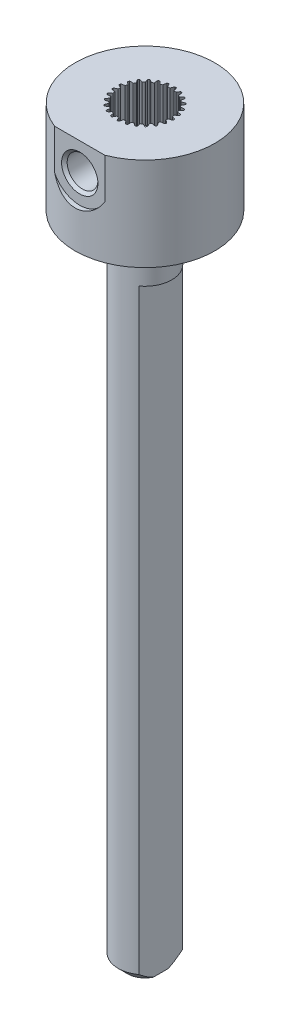
SolidWorks part; units mm, degrees
material "PBT General Purpose"
ref_plane "Front Plane" through (0, 0, 0) normal (0, 0, 1) x (1, 0, 0)
ref_plane "Top Plane" through (0, 0, 0) normal (0, 1, 0) x (1, 0, 0)
ref_plane "Right Plane" through (0, 0, 0) normal (1, 0, 0) x (0, 0, -1)
sketch "Sketch1" plane through (0, 0, 0) normal (0, 1, 0) x (1, 0, 0)
  circle A0 centre (0, 0) radius 2.875
  dimension "D1" = 5.75
extrude "Boss-Extrude1" add sketch "Sketch1" along normal mid plane 70
chamfer "Chamfer1" distance 1 angle 45 1 edges at (0, -35, 2.875)
sketch "Sketch2" plane through (0, 35, 0) normal (0, 1, 0) x (1, 0, 0)
  circle A0 centre (0, 0) radius 7.5
  dimension "D1" = 15
extrude "Boss-Extrude2" add sketch "Sketch2" along normal blind 10
sketch "Sketch3" plane through (0, 45, 0) normal (0, 1, 0) x (1, 0, 0)
  circle A0 centre (0, 0) radius 2.5
  dimension "D1" = 5
extrude "Cut-Extrude1" cut sketch "Sketch3" against normal blind 6
ref_plane "Plane1" through (0, 0, 10) normal (0, 0, 1) x (1, 0, 0)
sketch "Sketch5" plane through (0, 0, 10) normal (0, 0, 1) x (1, 0, 0)
  line L0 (0, 42) -> (0, 45) construction
  line L1 (2.5, 45) -> (-2.5, 45) construction
  line L2 (-3, 42) -> (-3, 45)
  line L3 (7.5, 45) -> (-7.5, 45) construction
  line L4 (-3, 45) -> (3, 45)
  line L5 (3, 45) -> (3, 42)
  arc A0 (-3, 42) -> (3, 42) centre (0, 42) ccw
  dimension "D1" = 6
  dimension "D2" = 3
extrude "Cut-Extrude3" cut sketch "Sketch5" against normal blind 3
sketch "Sketch4" plane through (0, 0, 10) normal (0, 0, 1) x (1, 0, 0)
  line L0 (0, 42) -> (0, 45) construction
  line L1 (7.5, 45) -> (-7.5, 45) construction
  circle A0 centre (0, 42) radius 1.65
  arc A2 (-2.6926, 40.6771) -> (2.6926, 40.6771) centre (0, 42) ccw construction
  dimension "D1" = 3.3
extrude "Cut-Extrude2" cut sketch "Sketch4" against normal up to next
chamfer "Chamfer2" distance 0.3 angle 45 1 edges at (1.65, 42, 7)
sketch "Sketch7" plane through (0, 45, 0) normal (0, 1, 0) x (1, 0, 0)
  line L1201 (2.7391, 0.4913) -> (2.7926, 0.5169)
  line L1202 (2.7002, 0.4763) -> (2.7391, 0.4913)
  line L1203 (2.7144, 0.3878) -> (2.7002, 0.4763)
  line L1204 (2.7256, 0.2988) -> (2.7144, 0.3878)
  line L1205 (2.7339, 0.2095) -> (2.7256, 0.2988)
  line L1206 (2.7753, 0.2046) -> (2.7339, 0.2095)
  line L1207 (2.8336, 0.193) -> (2.7753, 0.2046)
  line L1208 (2.8706, 0.1829) -> (2.8336, 0.193)
  line L1209 (2.8995, 0.1744) -> (2.8706, 0.1829)
  line L1210 (2.9507, 0.1568) -> (2.8995, 0.1744)
  line L1211 (2.9703, 0.1492) -> (2.9507, 0.1568)
  line L1212 (3.0285, 0.125) -> (2.9703, 0.1492)
  line L1213 (3.0613, 0.1091) -> (3.0285, 0.125)
  line L1214 (3.115, 0.0827) -> (3.0613, 0.1091)
  line L1215 (3.116, 0.0273) -> (3.115, 0.0827)
  line L1216 (3.116, -0.028) -> (3.116, 0.0273)
  line L1217 (3.115, -0.0834) -> (3.116, -0.028)
  line L1218 (3.0613, -0.1098) -> (3.115, -0.0834)
  line L1219 (3.0285, -0.1256) -> (3.0613, -0.1098)
  line L1220 (2.9703, -0.1499) -> (3.0285, -0.1256)
  line L1221 (2.9507, -0.1575) -> (2.9703, -0.1499)
  line L1222 (2.8994, -0.1751) -> (2.9507, -0.1575)
  line L1223 (2.8705, -0.1837) -> (2.8994, -0.1751)
  line L1224 (2.8335, -0.1938) -> (2.8705, -0.1837)
  line L1225 (2.7753, -0.2053) -> (2.8335, -0.1938)
  line L1226 (2.7339, -0.2102) -> (2.7753, -0.2053)
  line L1227 (2.7256, -0.2995) -> (2.7339, -0.2102)
  line L1228 (2.7144, -0.3884) -> (2.7256, -0.2995)
  line L1229 (2.7002, -0.477) -> (2.7144, -0.3884)
  line L1230 (2.7391, -0.492) -> (2.7002, -0.477)
  line L1231 (2.7927, -0.5177) -> (2.7391, -0.492)
  line L1232 (2.8259, -0.5367) -> (2.7927, -0.5177)
  line L1233 (2.8518, -0.5521) -> (2.8259, -0.5367)
  line L1234 (2.8971, -0.5819) -> (2.8518, -0.5521)
  line L1235 (2.9141, -0.5942) -> (2.8971, -0.5819)
  line L1236 (2.9645, -0.6321) -> (2.9141, -0.5942)
  line L1237 (2.9924, -0.6557) -> (2.9645, -0.6321)
  line L1238 (3.0378, -0.6946) -> (2.9924, -0.6557)
  line L1239 (3.025, -0.7484) -> (3.0378, -0.6946)
  line L1240 (3.0112, -0.8021) -> (3.025, -0.7484)
  line L1241 (2.9965, -0.8554) -> (3.0112, -0.8021)
  line L1242 (2.938, -0.8676) -> (2.9965, -0.8554)
  line L1243 (2.9022, -0.8749) -> (2.938, -0.8676)
  line L1244 (2.8398, -0.8838) -> (2.9022, -0.8749)
  line L1245 (2.8189, -0.8864) -> (2.8398, -0.8838)
  line L1246 (2.7649, -0.8907) -> (2.8189, -0.8864)
  line L1247 (2.7347, -0.8917) -> (2.7649, -0.8907)
  line L1248 (2.6964, -0.8924) -> (2.7347, -0.8917)
  line L1249 (2.6372, -0.8891) -> (2.6964, -0.8924)
  line L1250 (2.5959, -0.8835) -> (2.6372, -0.8891)
  line L1251 (2.5656, -0.9679) -> (2.5959, -0.8835)
  line L1252 (2.5326, -1.0513) -> (2.5656, -0.9679)
  line L1253 (2.4969, -1.1335) -> (2.5326, -1.0513)
  line L1254 (2.5308, -1.1577) -> (2.4969, -1.1335)
  line L1255 (2.5763, -1.196) -> (2.5308, -1.1577)
  line L1256 (2.6038, -1.2226) -> (2.5763, -1.196)
  line L1257 (2.625, -1.244) -> (2.6038, -1.2226)
  line L1258 (2.6615, -1.2841) -> (2.625, -1.244)
  line L1259 (2.6749, -1.3003) -> (2.6615, -1.2841)
  line L1260 (2.7143, -1.3495) -> (2.6749, -1.3003)
  line L1261 (2.7354, -1.3793) -> (2.7143, -1.3495)
  line L1262 (2.7697, -1.4282) -> (2.7354, -1.3793)
  line L1263 (2.7439, -1.4772) -> (2.7697, -1.4282)
  line L1264 (2.7172, -1.5257) -> (2.7439, -1.4772)
  line L1265 (2.6897, -1.5737) -> (2.7172, -1.5257)
  line L1266 (2.63, -1.571) -> (2.6897, -1.5737)
  line L1267 (2.5935, -1.5691) -> (2.63, -1.571)
  line L1268 (2.5308, -1.5623) -> (2.5935, -1.5691)
  line L1269 (2.51, -1.5596) -> (2.5308, -1.5623)
  line L1270 (2.4566, -1.5503) -> (2.51, -1.5596)
  line L1271 (2.4271, -1.5438) -> (2.4566, -1.5503)
  line L1272 (2.3898, -1.5349) -> (2.4271, -1.5438)
  line L1273 (2.3333, -1.517) -> (2.3898, -1.5349)
  line L1274 (2.2947, -1.5013) -> (2.3333, -1.517)
  line L1275 (2.2444, -1.5755) -> (2.2947, -1.5013)
  line L1276 (2.1917, -1.6481) -> (2.2444, -1.5755)
  line L1277 (2.1366, -1.7189) -> (2.1917, -1.6481)
  line L1278 (2.1635, -1.7507) -> (2.1366, -1.7189)
  line L1279 (2.198, -1.7991) -> (2.1635, -1.7507)
  line L1280 (2.218, -1.8317) -> (2.198, -1.7991)
  line L1281 (2.2333, -1.8577) -> (2.218, -1.8317)
  line L1282 (2.2586, -1.9056) -> (2.2333, -1.8577)
  line L1283 (2.2676, -1.9246) -> (2.2586, -1.9056)
  line L1284 (2.2935, -1.9821) -> (2.2676, -1.9246)
  line L1285 (2.3065, -2.0162) -> (2.2935, -1.9821)
  line L1286 (2.3276, -2.0722) -> (2.3065, -2.0162)
  line L1287 (2.2904, -2.1132) -> (2.3276, -2.0722)
  line L1288 (2.2525, -2.1535) -> (2.2904, -2.1132)
  line L1289 (2.2139, -2.1932) -> (2.2525, -2.1535)
  line L1290 (2.1567, -2.1757) -> (2.2139, -2.1932)
  line L1291 (2.1219, -2.1648) -> (2.1567, -2.1757)
  line L1292 (2.0629, -2.1426) -> (2.1219, -2.1648)
  line L1293 (2.0434, -2.1348) -> (2.0629, -2.1426)
  line L1294 (1.9939, -2.1125) -> (2.0434, -2.1348)
  line L1295 (1.967, -2.0989) -> (1.9939, -2.1125)
  line L1296 (1.9331, -2.081) -> (1.967, -2.0989)
  line L1297 (1.8828, -2.0496) -> (1.9331, -2.081)
  line L1298 (1.8493, -2.0248) -> (1.8828, -2.0496)
  line L1299 (1.7821, -2.0842) -> (1.8493, -2.0248)
  line L1300 (1.713, -2.1413) -> (1.7821, -2.0842)
  line L1301 (1.6421, -2.1962) -> (1.713, -2.1413)
  line L1302 (1.6602, -2.2338) -> (1.6421, -2.1962)
  line L1303 (1.6816, -2.2892) -> (1.6602, -2.2338)
  line L1304 (1.6929, -2.3258) -> (1.6816, -2.2892)
  line L1305 (1.7012, -2.3548) -> (1.6929, -2.3258)
  line L1306 (1.7138, -2.4075) -> (1.7012, -2.3548)
  line L1307 (1.7178, -2.4281) -> (1.7138, -2.4075)
  line L1308 (1.7286, -2.4902) -> (1.7178, -2.4281)
  line L1309 (1.7327, -2.5265) -> (1.7286, -2.4902)
  line L1310 (1.7392, -2.5859) -> (1.7327, -2.5265)
  line L1311 (1.693, -2.6164) -> (1.7392, -2.5859)
  line L1312 (1.6463, -2.6461) -> (1.693, -2.6164)
  line L1313 (1.599, -2.6749) -> (1.6463, -2.6461)
  line L1314 (1.548, -2.6437) -> (1.599, -2.6749)
  line L1315 (1.517, -2.6245) -> (1.548, -2.6437)
  line L1316 (1.4653, -2.5883) -> (1.517, -2.6245)
  line L1317 (1.4484, -2.5759) -> (1.4653, -2.5883)
  line L1318 (1.406, -2.542) -> (1.4484, -2.5759)
  line L1319 (1.3833, -2.5221) -> (1.406, -2.542)
  line L1320 (1.355, -2.4964) -> (1.3833, -2.5221)
  line L1321 (1.314, -2.4534) -> (1.355, -2.4964)
  line L1322 (1.2878, -2.4211) -> (1.314, -2.4534)
  line L1323 (1.2079, -2.4619) -> (1.2878, -2.4211)
  line L1324 (1.1268, -2.5001) -> (1.2079, -2.4619)
  line L1325 (1.0444, -2.5356) -> (1.1268, -2.5001)
  line L1326 (1.0526, -2.5765) -> (1.0444, -2.5356)
  line L1327 (1.0596, -2.6355) -> (1.0526, -2.5765)
  line L1328 (1.0614, -2.6737) -> (1.0596, -2.6355)
  line L1329 (1.0622, -2.7038) -> (1.0614, -2.6737)
  line L1330 (1.0613, -2.758) -> (1.0622, -2.7038)
  line L1331 (1.0601, -2.779) -> (1.0613, -2.758)
  line L1332 (1.0551, -2.8419) -> (1.0601, -2.779)
  line L1333 (1.0501, -2.878) -> (1.0551, -2.8419)
  line L1334 (1.0416, -2.9372) -> (1.0501, -2.878)
  line L1335 (0.9892, -2.9552) -> (1.0416, -2.9372)
  line L1336 (0.9366, -2.9723) -> (0.9892, -2.9552)
  line L1337 (0.8837, -2.9885) -> (0.9366, -2.9723)
  line L1338 (0.842, -2.9456) -> (0.8837, -2.9885)
  line L1339 (0.8167, -2.9193) -> (0.842, -2.9456)
  line L1340 (0.7757, -2.8714) -> (0.8167, -2.9193)
  line L1341 (0.7623, -2.8552) -> (0.7757, -2.8714)
  line L1342 (0.7298, -2.8118) -> (0.7623, -2.8552)
  line L1343 (0.7127, -2.7869) -> (0.7298, -2.8118)
  line L1344 (0.6917, -2.7549) -> (0.7127, -2.7869)
  line L1345 (0.6627, -2.7031) -> (0.6917, -2.7549)
  line L1346 (0.6453, -2.6653) -> (0.6627, -2.7031)
  line L1347 (0.5578, -2.6849) -> (0.6453, -2.6653)
  line L1348 (0.4697, -2.7018) -> (0.5578, -2.6849)
  line L1349 (0.3811, -2.7157) -> (0.4697, -2.7018)
  line L1350 (0.3789, -2.7573) -> (0.3811, -2.7157)
  line L1351 (0.371, -2.8162) -> (0.3789, -2.7573)
  line L1352 (0.3632, -2.8537) -> (0.371, -2.8162)
  line L1353 (0.3565, -2.8831) -> (0.3632, -2.8537)
  line L1354 (0.3422, -2.9353) -> (0.3565, -2.8831)
  line L1355 (0.3358, -2.9553) -> (0.3422, -2.9353)
  line L1356 (0.3153, -3.015) -> (0.3358, -2.9553)
  line L1357 (0.3015, -3.0487) -> (0.3153, -3.015)
  line L1358 (0.2785, -3.1039) -> (0.3015, -3.0487)
  line L1359 (0.2233, -3.1084) -> (0.2785, -3.1039)
  line L1360 (0.1681, -3.1119) -> (0.2233, -3.1084)
  line L1361 (0.1128, -3.1144) -> (0.1681, -3.1119)
  line L1362 (0.0831, -3.0625) -> (0.1128, -3.1144)
  line L1363 (0.0651, -3.0307) -> (0.0831, -3.0625)
  line L1364 (0.0373, -2.9741) -> (0.0651, -3.0307)
  line L1365 (0.0284, -2.955) -> (0.0373, -2.9741)
  line L1366 (0.0076, -2.905) -> (0.0284, -2.955)
  line L1367 (-0.0027, -2.8766) -> (0.0076, -2.905)
  line L1368 (-0.0151, -2.8404) -> (-0.0027, -2.8766)
  line L1369 (-0.0303, -2.783) -> (-0.0151, -2.8404)
  line L1370 (-0.0377, -2.742) -> (-0.0303, -2.783)
  line L1371 (-0.1274, -2.7393) -> (-0.0377, -2.742)
  line L1372 (-0.2169, -2.7337) -> (-0.1274, -2.7393)
  line L1373 (-0.3061, -2.7251) -> (-0.2169, -2.7337)
  line L1374 (-0.3186, -2.7649) -> (-0.3061, -2.7251)
  line L1375 (-0.341, -2.82) -> (-0.3186, -2.7649)
  line L1376 (-0.3578, -2.8543) -> (-0.341, -2.82)
  line L1377 (-0.3716, -2.8812) -> (-0.3578, -2.8543)
  line L1378 (-0.3985, -2.9282) -> (-0.3716, -2.8812)
  line L1379 (-0.4097, -2.946) -> (-0.3985, -2.9282)
  line L1380 (-0.4443, -2.9986) -> (-0.4097, -2.946)
  line L1381 (-0.4661, -3.0279) -> (-0.4443, -2.9986)
  line L1382 (-0.5021, -3.0757) -> (-0.4661, -3.0279)
  line L1383 (-0.5566, -3.0663) -> (-0.5021, -3.0757)
  line L1384 (-0.611, -3.0559) -> (-0.5566, -3.0663)
  line L1385 (-0.6652, -3.0446) -> (-0.611, -3.0559)
  line L1386 (-0.6811, -2.9869) -> (-0.6652, -3.0446)
  line L1387 (-0.6905, -2.9517) -> (-0.6811, -2.9869)
  line L1388 (-0.7034, -2.8899) -> (-0.6905, -2.9517)
  line L1389 (-0.7073, -2.8693) -> (-0.7034, -2.8899)
  line L1390 (-0.7149, -2.8156) -> (-0.7073, -2.8693)
  line L1391 (-0.7179, -2.7856) -> (-0.7149, -2.8156)
  line L1392 (-0.7209, -2.7474) -> (-0.7179, -2.7856)
  line L1393 (-0.7214, -2.6881) -> (-0.7209, -2.7474)
  line L1394 (-0.7184, -2.6465) -> (-0.7214, -2.6881)
  line L1395 (-0.8045, -2.6216) -> (-0.7184, -2.6465)
  line L1396 (-0.8898, -2.5939) -> (-0.8045, -2.6216)
  line L1397 (-0.9741, -2.5634) -> (-0.8898, -2.5939)
  line L1398 (-0.9962, -2.5988) -> (-0.9741, -2.5634)
  line L1399 (-1.0315, -2.6466) -> (-0.9962, -2.5988)
  line L1400 (-1.0563, -2.6757) -> (-1.0315, -2.6466)
  line L1401 (-1.0763, -2.6982) -> (-1.0563, -2.6757)
  line L1402 (-1.1141, -2.7371) -> (-1.0763, -2.6982)
  line L1403 (-1.1294, -2.7516) -> (-1.1141, -2.7371)
  line L1404 (-1.176, -2.7939) -> (-1.1294, -2.7516)
  line L1405 (-1.2044, -2.8169) -> (-1.176, -2.7939)
  line L1406 (-1.2511, -2.8542) -> (-1.2044, -2.8169)
  line L1407 (-1.3016, -2.8315) -> (-1.2511, -2.8542)
  line L1408 (-1.3517, -2.808) -> (-1.3016, -2.8315)
  line L1409 (-1.4014, -2.7835) -> (-1.3517, -2.808)
  line L1410 (-1.4024, -2.7237) -> (-1.4014, -2.7835)
  line L1411 (-1.4028, -2.6872) -> (-1.4024, -2.7237)
  line L1412 (-1.3999, -2.6242) -> (-1.4028, -2.6872)
  line L1413 (-1.3985, -2.6032) -> (-1.3999, -2.6242)
  line L1414 (-1.3926, -2.5494) -> (-1.3985, -2.6032)
  line L1415 (-1.388, -2.5195) -> (-1.3926, -2.5494)
  line L1416 (-1.3814, -2.4818) -> (-1.388, -2.5195)
  line L1417 (-1.3671, -2.4242) -> (-1.3814, -2.4818)
  line L1418 (-1.3539, -2.3847) -> (-1.3671, -2.4242)
  line L1419 (-1.4311, -2.3392) -> (-1.3539, -2.3847)
  line L1420 (-1.5068, -2.2911) -> (-1.4311, -2.3392)
  line L1421 (-1.5809, -2.2406) -> (-1.5068, -2.2911)
  line L1422 (-1.6111, -2.2694) -> (-1.5809, -2.2406)
  line L1423 (-1.6572, -2.3069) -> (-1.6111, -2.2694)
  line L1424 (-1.6885, -2.3289) -> (-1.6572, -2.3069)
  line L1425 (-1.7135, -2.3458) -> (-1.6885, -2.3289)
  line L1426 (-1.7597, -2.3741) -> (-1.7135, -2.3458)
  line L1427 (-1.7781, -2.3843) -> (-1.7597, -2.3741)
  line L1428 (-1.8338, -2.4137) -> (-1.7781, -2.3843)
  line L1429 (-1.867, -2.4289) -> (-1.8338, -2.4137)
  line L1430 (-1.9216, -2.4534) -> (-1.867, -2.4289)
  line L1431 (-1.9648, -2.4189) -> (-1.9216, -2.4534)
  line L1432 (-2.0075, -2.3836) -> (-1.9648, -2.4189)
  line L1433 (-2.0495, -2.3476) -> (-2.0075, -2.3836)
  line L1434 (-2.0356, -2.2894) -> (-2.0495, -2.3476)
  line L1435 (-2.0269, -2.2539) -> (-2.0356, -2.2894)
  line L1436 (-2.0085, -2.1936) -> (-2.0269, -2.2539)
  line L1437 (-2.0019, -2.1737) -> (-2.0085, -2.1936)
  line L1438 (-1.9828, -2.1229) -> (-2.0019, -2.1737)
  line L1439 (-1.9709, -2.0952) -> (-1.9828, -2.1229)
  line L1440 (-1.9551, -2.0603) -> (-1.9709, -2.0952)
  line L1441 (-1.9269, -2.0081) -> (-1.9551, -2.0603)
  line L1442 (-1.9043, -1.9731) -> (-1.9269, -2.0081)
  line L1443 (-1.9678, -1.9098) -> (-1.9043, -1.9731)
  line L1444 (-2.0292, -1.8444) -> (-1.9678, -1.9098)
  line L1445 (-2.0884, -1.777) -> (-2.0292, -1.8444)
  line L1446 (-2.1247, -1.7975) -> (-2.0884, -1.777)
  line L1447 (-2.1787, -1.8223) -> (-2.1247, -1.7975)
  line L1448 (-2.2145, -1.8359) -> (-2.1787, -1.8223)
  line L1449 (-2.2429, -1.846) -> (-2.2145, -1.8359)
  line L1450 (-2.2947, -1.8619) -> (-2.2429, -1.846)
  line L1451 (-2.3151, -1.8672) -> (-2.2947, -1.8619)
  line L1452 (-2.3764, -1.8818) -> (-2.3151, -1.8672)
  line L1453 (-2.4123, -1.8882) -> (-2.3764, -1.8818)
  line L1454 (-2.4712, -1.8984) -> (-2.4123, -1.8882)
  line L1455 (-2.5045, -1.8542) -> (-2.4712, -1.8984)
  line L1456 (-2.5371, -1.8095) -> (-2.5045, -1.8542)
  line L1457 (-2.5688, -1.7641) -> (-2.5371, -1.8095)
  line L1458 (-2.5409, -1.7112) -> (-2.5688, -1.7641)
  line L1459 (-2.5237, -1.679) -> (-2.5409, -1.7112)
  line L1460 (-2.4908, -1.6253) -> (-2.5237, -1.679)
  line L1461 (-2.4795, -1.6075) -> (-2.4908, -1.6253)
  line L1462 (-2.4483, -1.5631) -> (-2.4795, -1.6075)
  line L1463 (-2.4299, -1.5392) -> (-2.4483, -1.5631)
  line L1464 (-2.406, -1.5093) -> (-2.4299, -1.5392)
  line L1465 (-2.3657, -1.4658) -> (-2.406, -1.5093)
  line L1466 (-2.3351, -1.4375) -> (-2.3657, -1.4658)
  line L1467 (-2.3808, -1.3604) -> (-2.3351, -1.4375)
  line L1468 (-2.424, -1.2818) -> (-2.3808, -1.3604)
  line L1469 (-2.4646, -1.2019) -> (-2.424, -1.2818)
  line L1470 (-2.5049, -1.2126) -> (-2.4646, -1.2019)
  line L1471 (-2.5634, -1.2233) -> (-2.5049, -1.2126)
  line L1472 (-2.6014, -1.2275) -> (-2.5634, -1.2233)
  line L1473 (-2.6314, -1.2302) -> (-2.6014, -1.2275)
  line L1474 (-2.6856, -1.2327) -> (-2.6314, -1.2302)
  line L1475 (-2.7066, -1.2328) -> (-2.6856, -1.2327)
  line L1476 (-2.7696, -1.2317) -> (-2.7066, -1.2328)
  line L1477 (-2.806, -1.229) -> (-2.7696, -1.2317)
  line L1478 (-2.8656, -1.2242) -> (-2.806, -1.229)
  line L1479 (-2.8869, -1.1731) -> (-2.8656, -1.2242)
  line L1480 (-2.9073, -1.1217) -> (-2.8869, -1.1731)
  line L1481 (-2.9267, -1.0699) -> (-2.9073, -1.1217)
  line L1482 (-2.8866, -1.0255) -> (-2.9267, -1.0699)
  line L1483 (-2.8619, -0.9987) -> (-2.8866, -1.0255)
  line L1484 (-2.8166, -0.9547) -> (-2.8619, -0.9987)
  line L1485 (-2.8013, -0.9404) -> (-2.8166, -0.9547)
  line L1486 (-2.7601, -0.9052) -> (-2.8013, -0.9404)
  line L1487 (-2.7363, -0.8866) -> (-2.7601, -0.9052)
  line L1488 (-2.7057, -0.8636) -> (-2.7363, -0.8866)
  line L1489 (-2.6558, -0.8314) -> (-2.7057, -0.8636)
  line L1490 (-2.6191, -0.8117) -> (-2.6558, -0.8314)
  line L1491 (-2.6442, -0.7256) -> (-2.6191, -0.8117)
  line L1492 (-2.6665, -0.6387) -> (-2.6442, -0.7256)
  line L1493 (-2.686, -0.5512) -> (-2.6665, -0.6387)
  line L1494 (-2.7277, -0.5515) -> (-2.686, -0.5512)
  line L1495 (-2.787, -0.5473) -> (-2.7277, -0.5515)
  line L1496 (-2.8249, -0.542) -> (-2.787, -0.5473)
  line L1497 (-2.8546, -0.5371) -> (-2.8249, -0.542)
  line L1498 (-2.9077, -0.5261) -> (-2.8546, -0.5371)
  line L1499 (-2.928, -0.5209) -> (-2.9077, -0.5261)
  line L1500 (-2.9888, -0.5042) -> (-2.928, -0.5209)
  line L1501 (-3.0234, -0.4926) -> (-2.9888, -0.5042)
  line L1502 (-3.08, -0.4731) -> (-3.0234, -0.4926)
  line L1503 (-3.0879, -0.4183) -> (-3.08, -0.4731)
  line L1504 (-3.0948, -0.3634) -> (-3.0879, -0.4183)
  line L1505 (-3.1008, -0.3084) -> (-3.0948, -0.3634)
  line L1506 (-3.0508, -0.2755) -> (-3.1008, -0.3084)
  line L1507 (-3.0202, -0.2556) -> (-3.0508, -0.2755)
  line L1508 (-2.9655, -0.2243) -> (-3.0202, -0.2556)
  line L1509 (-2.9471, -0.2142) -> (-2.9655, -0.2243)
  line L1510 (-2.8984, -0.1903) -> (-2.9471, -0.2142)
  line L1511 (-2.8707, -0.1782) -> (-2.8984, -0.1903)
  line L1512 (-2.8353, -0.1636) -> (-2.8707, -0.1782)
  line L1513 (-2.7791, -0.1448) -> (-2.8353, -0.1636)
  line L1514 (-2.7386, -0.1348) -> (-2.7791, -0.1448)
  line L1515 (-2.7415, -0.0452) -> (-2.7386, -0.1348)
  line L1516 (-2.7415, 0.0445) -> (-2.7415, -0.0452)
  line L1517 (-2.7386, 0.1341) -> (-2.7415, 0.0445)
  line L1518 (-2.7791, 0.1441) -> (-2.7386, 0.1341)
  line L1519 (-2.8355, 0.1629) -> (-2.7791, 0.1441)
  line L1520 (-2.8708, 0.1776) -> (-2.8355, 0.1629)
  line L1521 (-2.8984, 0.1897) -> (-2.8708, 0.1776)
  line L1522 (-2.9471, 0.2135) -> (-2.8984, 0.1897)
  line L1523 (-2.9655, 0.2236) -> (-2.9471, 0.2135)
  line L1524 (-3.0202, 0.2549) -> (-2.9655, 0.2236)
  line L1525 (-3.0508, 0.2748) -> (-3.0202, 0.2549)
  line L1526 (-3.1008, 0.3077) -> (-3.0508, 0.2748)
  line L1527 (-3.0948, 0.3627) -> (-3.1008, 0.3077)
  line L1528 (-3.0879, 0.4176) -> (-3.0948, 0.3627)
  line L1529 (-3.08, 0.4724) -> (-3.0879, 0.4176)
  line L1530 (-3.0234, 0.4919) -> (-3.08, 0.4724)
  line L1531 (-2.9888, 0.5035) -> (-3.0234, 0.4919)
  line L1532 (-2.928, 0.5203) -> (-2.9888, 0.5035)
  line L1533 (-2.9077, 0.5254) -> (-2.928, 0.5203)
  line L1534 (-2.8546, 0.5365) -> (-2.9077, 0.5254)
  line L1535 (-2.8248, 0.5413) -> (-2.8546, 0.5365)
  line L1536 (-2.7868, 0.5467) -> (-2.8248, 0.5413)
  line L1537 (-2.7277, 0.5509) -> (-2.7868, 0.5467)
  line L1538 (-2.686, 0.5505) -> (-2.7277, 0.5509)
  line L1539 (-2.6665, 0.638) -> (-2.686, 0.5505)
  line L1540 (-2.6442, 0.7249) -> (-2.6665, 0.638)
  line L1541 (-2.6191, 0.811) -> (-2.6442, 0.7249)
  line L1542 (-2.6558, 0.8307) -> (-2.6191, 0.811)
  line L1543 (-2.7058, 0.863) -> (-2.6558, 0.8307)
  line L1544 (-2.7364, 0.8859) -> (-2.7058, 0.863)
  line L1545 (-2.7601, 0.9045) -> (-2.7364, 0.8859)
  line L1546 (-2.8013, 0.9397) -> (-2.7601, 0.9045)
  line L1547 (-2.8166, 0.9541) -> (-2.8013, 0.9397)
  line L1548 (-2.8619, 0.998) -> (-2.8166, 0.9541)
  line L1549 (-2.8866, 1.0249) -> (-2.8619, 0.998)
  line L1550 (-2.9267, 1.0692) -> (-2.8866, 1.0249)
  line L1551 (-2.9073, 1.121) -> (-2.9267, 1.0692)
  line L1552 (-2.8869, 1.1724) -> (-2.9073, 1.121)
  line L1553 (-2.8656, 1.2235) -> (-2.8869, 1.1724)
  line L1554 (-2.806, 1.2283) -> (-2.8656, 1.2235)
  line L1555 (-2.7696, 1.231) -> (-2.806, 1.2283)
  line L1556 (-2.7066, 1.2321) -> (-2.7696, 1.231)
  line L1557 (-2.6855, 1.232) -> (-2.7066, 1.2321)
  line L1558 (-2.6314, 1.2295) -> (-2.6855, 1.232)
  line L1559 (-2.6013, 1.2268) -> (-2.6314, 1.2295)
  line L1560 (-2.5632, 1.2226) -> (-2.6013, 1.2268)
  line L1561 (-2.5049, 1.2119) -> (-2.5632, 1.2226)
  line L1562 (-2.4646, 1.2012) -> (-2.5049, 1.2119)
  line L1563 (-2.424, 1.2811) -> (-2.4646, 1.2012)
  line L1564 (-2.3808, 1.3597) -> (-2.424, 1.2811)
  line L1565 (-2.3351, 1.4368) -> (-2.3808, 1.3597)
  line L1566 (-2.3657, 1.4651) -> (-2.3351, 1.4368)
  line L1567 (-2.4061, 1.5088) -> (-2.3657, 1.4651)
  line L1568 (-2.43, 1.5386) -> (-2.4061, 1.5088)
  line L1569 (-2.4484, 1.5625) -> (-2.43, 1.5386)
  line L1570 (-2.4795, 1.6068) -> (-2.4484, 1.5625)
  line L1571 (-2.4908, 1.6246) -> (-2.4795, 1.6068)
  line L1572 (-2.5237, 1.6784) -> (-2.4908, 1.6246)
  line L1573 (-2.5409, 1.7105) -> (-2.5237, 1.6784)
  line L1574 (-2.5688, 1.7634) -> (-2.5409, 1.7105)
  line L1575 (-2.5371, 1.8088) -> (-2.5688, 1.7634)
  line L1576 (-2.5045, 1.8536) -> (-2.5371, 1.8088)
  line L1577 (-2.4712, 1.8977) -> (-2.5045, 1.8536)
  line L1578 (-2.4123, 1.8876) -> (-2.4712, 1.8977)
  line L1579 (-2.3764, 1.8811) -> (-2.4123, 1.8876)
  line L1580 (-2.315, 1.8665) -> (-2.3764, 1.8811)
  line L1581 (-2.2947, 1.8612) -> (-2.315, 1.8665)
  line L1582 (-2.2429, 1.8453) -> (-2.2947, 1.8612)
  line L1583 (-2.2144, 1.8352) -> (-2.2429, 1.8453)
  line L1584 (-2.1786, 1.8216) -> (-2.2144, 1.8352)
  line L1585 (-2.1247, 1.7968) -> (-2.1786, 1.8216)
  line L1586 (-2.0884, 1.7764) -> (-2.1247, 1.7968)
  line L1587 (-2.0292, 1.8437) -> (-2.0884, 1.7764)
  line L1588 (-1.9678, 1.9091) -> (-2.0292, 1.8437)
  line L1589 (-1.9043, 1.9724) -> (-1.9678, 1.9091)
  line L1590 (-1.927, 2.0074) -> (-1.9043, 1.9724)
  line L1591 (-1.9552, 2.0597) -> (-1.927, 2.0074)
  line L1592 (-1.9709, 2.0946) -> (-1.9552, 2.0597)
  line L1593 (-1.9828, 2.1223) -> (-1.9709, 2.0946)
  line L1594 (-2.0019, 2.173) -> (-1.9828, 2.1223)
  line L1595 (-2.0085, 2.193) -> (-2.0019, 2.173)
  line L1596 (-2.0269, 2.2532) -> (-2.0085, 2.193)
  line L1597 (-2.0356, 2.2887) -> (-2.0269, 2.2532)
  line L1598 (-2.0495, 2.3469) -> (-2.0356, 2.2887)
  line L1599 (-2.0075, 2.3829) -> (-2.0495, 2.3469)
  line L1600 (-1.9648, 2.4182) -> (-2.0075, 2.3829)
  line L1601 (-1.9216, 2.4527) -> (-1.9648, 2.4182)
  line L1602 (-1.867, 2.4282) -> (-1.9216, 2.4527)
  line L1603 (-1.8338, 2.413) -> (-1.867, 2.4282)
  line L1604 (-1.7781, 2.3836) -> (-1.8338, 2.413)
  line L1605 (-1.7597, 2.3734) -> (-1.7781, 2.3836)
  line L1606 (-1.7134, 2.3451) -> (-1.7597, 2.3734)
  line L1607 (-1.6884, 2.3282) -> (-1.7134, 2.3451)
  line L1608 (-1.657, 2.3062) -> (-1.6884, 2.3282)
  line L1609 (-1.6111, 2.2687) -> (-1.657, 2.3062)
  line L1610 (-1.5809, 2.2399) -> (-1.6111, 2.2687)
  line L1611 (-1.5068, 2.2904) -> (-1.5809, 2.2399)
  line L1612 (-1.4311, 2.3385) -> (-1.5068, 2.2904)
  line L1613 (-1.3539, 2.384) -> (-1.4311, 2.3385)
  line L1614 (-1.3671, 2.4236) -> (-1.3539, 2.384)
  line L1615 (-1.3814, 2.4812) -> (-1.3671, 2.4236)
  line L1616 (-1.388, 2.5189) -> (-1.3814, 2.4812)
  line L1617 (-1.3926, 2.5487) -> (-1.388, 2.5189)
  line L1618 (-1.3985, 2.6026) -> (-1.3926, 2.5487)
  line L1619 (-1.3999, 2.6236) -> (-1.3985, 2.6026)
  line L1620 (-1.4028, 2.6865) -> (-1.3999, 2.6236)
  line L1621 (-1.4024, 2.723) -> (-1.4028, 2.6865)
  line L1622 (-1.4014, 2.7828) -> (-1.4024, 2.723)
  line L1623 (-1.3517, 2.8073) -> (-1.4014, 2.7828)
  line L1624 (-1.3016, 2.8308) -> (-1.3517, 2.8073)
  line L1625 (-1.2511, 2.8535) -> (-1.3016, 2.8308)
  line L1626 (-1.2044, 2.8162) -> (-1.2511, 2.8535)
  line L1627 (-1.176, 2.7932) -> (-1.2044, 2.8162)
  line L1628 (-1.1293, 2.7509) -> (-1.176, 2.7932)
  line L1629 (-1.1141, 2.7364) -> (-1.1293, 2.7509)
  line L1630 (-1.0763, 2.6975) -> (-1.1141, 2.7364)
  line L1631 (-1.0563, 2.6749) -> (-1.0763, 2.6975)
  line L1632 (-1.0314, 2.6458) -> (-1.0563, 2.6749)
  line L1633 (-0.9961, 2.5981) -> (-1.0314, 2.6458)
  line L1634 (-0.9741, 2.5627) -> (-0.9961, 2.5981)
  line L1635 (-0.8898, 2.5932) -> (-0.9741, 2.5627)
  line L1636 (-0.8045, 2.6209) -> (-0.8898, 2.5932)
  line L1637 (-0.7184, 2.6458) -> (-0.8045, 2.6209)
  line L1638 (-0.7214, 2.6874) -> (-0.7184, 2.6458)
  line L1639 (-0.7209, 2.7468) -> (-0.7214, 2.6874)
  line L1640 (-0.7179, 2.785) -> (-0.7209, 2.7468)
  line L1641 (-0.7149, 2.815) -> (-0.7179, 2.785)
  line L1642 (-0.7073, 2.8686) -> (-0.7149, 2.815)
  line L1643 (-0.7034, 2.8893) -> (-0.7073, 2.8686)
  line L1644 (-0.6905, 2.951) -> (-0.7034, 2.8893)
  line L1645 (-0.6811, 2.9862) -> (-0.6905, 2.951)
  line L1646 (-0.6652, 3.0439) -> (-0.6811, 2.9862)
  line L1647 (-0.611, 3.0552) -> (-0.6652, 3.0439)
  line L1648 (-0.5566, 3.0656) -> (-0.611, 3.0552)
  line L1649 (-0.5021, 3.075) -> (-0.5566, 3.0656)
  line L1650 (-0.4661, 3.0272) -> (-0.5021, 3.075)
  line L1651 (-0.4444, 2.998) -> (-0.4661, 3.0272)
  line L1652 (-0.4097, 2.9453) -> (-0.4444, 2.998)
  line L1653 (-0.3984, 2.9275) -> (-0.4097, 2.9453)
  line L1654 (-0.3716, 2.8804) -> (-0.3984, 2.9275)
  line L1655 (-0.3578, 2.8536) -> (-0.3716, 2.8804)
  line L1656 (-0.3409, 2.8192) -> (-0.3578, 2.8536)
  line L1657 (-0.3186, 2.7642) -> (-0.3409, 2.8192)
  line L1658 (-0.3061, 2.7244) -> (-0.3186, 2.7642)
  line L1659 (-0.2169, 2.733) -> (-0.3061, 2.7244)
  line L1660 (-0.1274, 2.7386) -> (-0.2169, 2.733)
  line L1661 (-0.0377, 2.7413) -> (-0.1274, 2.7386)
  line L1662 (-0.0303, 2.7824) -> (-0.0377, 2.7413)
  line L1663 (-0.015, 2.8398) -> (-0.0303, 2.7824)
  line L1664 (-0.0026, 2.876) -> (-0.015, 2.8398)
  line L1665 (0.0077, 2.9043) -> (-0.0026, 2.876)
  line L1666 (0.0284, 2.9544) -> (0.0077, 2.9043)
  line L1667 (0.0373, 2.9734) -> (0.0284, 2.9544)
  line L1668 (0.0651, 3.03) -> (0.0373, 2.9734)
  line L1669 (0.0831, 3.0618) -> (0.0651, 3.03)
  line L1670 (0.1128, 3.1137) -> (0.0831, 3.0618)
  line L1671 (0.1681, 3.1112) -> (0.1128, 3.1137)
  line L1672 (0.2233, 3.1077) -> (0.1681, 3.1112)
  line L1673 (0.2785, 3.1033) -> (0.2233, 3.1077)
  line L1674 (0.3015, 3.048) -> (0.2785, 3.1033)
  line L1675 (0.3153, 3.0143) -> (0.3015, 3.048)
  line L1676 (0.3358, 2.9546) -> (0.3153, 3.0143)
  line L1677 (0.3422, 2.9346) -> (0.3358, 2.9546)
  line L1678 (0.3565, 2.8823) -> (0.3422, 2.9346)
  line L1679 (0.3632, 2.8529) -> (0.3565, 2.8823)
  line L1680 (0.371, 2.8154) -> (0.3632, 2.8529)
  line L1681 (0.3789, 2.7566) -> (0.371, 2.8154)
  line L1682 (0.3811, 2.715) -> (0.3789, 2.7566)
  line L1683 (0.4697, 2.7011) -> (0.3811, 2.715)
  line L1684 (0.5578, 2.6843) -> (0.4697, 2.7011)
  line L1685 (0.6453, 2.6646) -> (0.5578, 2.6843)
  line L1686 (0.6627, 2.7025) -> (0.6453, 2.6646)
  line L1687 (0.6917, 2.7543) -> (0.6627, 2.7025)
  line L1688 (0.7128, 2.7863) -> (0.6917, 2.7543)
  line L1689 (0.7298, 2.8112) -> (0.7128, 2.7863)
  line L1690 (0.7624, 2.8545) -> (0.7298, 2.8112)
  line L1691 (0.7757, 2.8707) -> (0.7624, 2.8545)
  line L1692 (0.8167, 2.9186) -> (0.7757, 2.8707)
  line L1693 (0.842, 2.9449) -> (0.8167, 2.9186)
  line L1694 (0.8837, 2.9878) -> (0.842, 2.9449)
  line L1695 (0.9366, 2.9716) -> (0.8837, 2.9878)
  line L1696 (0.9892, 2.9545) -> (0.9366, 2.9716)
  line L1697 (1.0416, 2.9365) -> (0.9892, 2.9545)
  line L1698 (1.0501, 2.8773) -> (1.0416, 2.9365)
  line L1699 (1.0551, 2.8412) -> (1.0501, 2.8773)
  line L1700 (1.0601, 2.7783) -> (1.0551, 2.8412)
  line L1701 (1.0613, 2.7573) -> (1.0601, 2.7783)
  line L1702 (1.0622, 2.7031) -> (1.0613, 2.7573)
  line L1703 (1.0614, 2.6729) -> (1.0622, 2.7031)
  line L1704 (1.0596, 2.6347) -> (1.0614, 2.6729)
  line L1705 (1.0526, 2.5758) -> (1.0596, 2.6347)
  line L1706 (1.0444, 2.5349) -> (1.0526, 2.5758)
  line L1707 (1.1268, 2.4994) -> (1.0444, 2.5349)
  line L1708 (1.2079, 2.4612) -> (1.1268, 2.4994)
  line L1709 (1.2878, 2.4204) -> (1.2079, 2.4612)
  line L1710 (1.3141, 2.4528) -> (1.2878, 2.4204)
  line L1711 (1.3551, 2.4958) -> (1.3141, 2.4528)
  line L1712 (1.3834, 2.5215) -> (1.3551, 2.4958)
  line L1713 (1.4061, 2.5414) -> (1.3834, 2.5215)
  line L1714 (1.4484, 2.5752) -> (1.4061, 2.5414)
  line L1715 (1.4653, 2.5876) -> (1.4484, 2.5752)
  line L1716 (1.517, 2.6238) -> (1.4653, 2.5876)
  line L1717 (1.548, 2.643) -> (1.517, 2.6238)
  line L1718 (1.599, 2.6742) -> (1.548, 2.643)
  line L1719 (1.6463, 2.6454) -> (1.599, 2.6742)
  line L1720 (1.693, 2.6157) -> (1.6463, 2.6454)
  line L1721 (1.7392, 2.5852) -> (1.693, 2.6157)
  line L1722 (1.7327, 2.5258) -> (1.7392, 2.5852)
  line L1723 (1.7286, 2.4895) -> (1.7327, 2.5258)
  line L1724 (1.7178, 2.4274) -> (1.7286, 2.4895)
  line L1725 (1.7138, 2.4067) -> (1.7178, 2.4274)
  line L1726 (1.7012, 2.354) -> (1.7138, 2.4067)
  line L1727 (1.6929, 2.325) -> (1.7012, 2.354)
  line L1728 (1.6816, 2.2884) -> (1.6929, 2.325)
  line L1729 (1.6602, 2.2331) -> (1.6816, 2.2884)
  line L1730 (1.6421, 2.1955) -> (1.6602, 2.2331)
  line L1731 (1.713, 2.1407) -> (1.6421, 2.1955)
  line L1732 (1.7821, 2.0835) -> (1.713, 2.1407)
  line L1733 (1.8493, 2.0241) -> (1.7821, 2.0835)
  line L1734 (1.8828, 2.0489) -> (1.8493, 2.0241)
  line L1735 (1.9333, 2.0804) -> (1.8828, 2.0489)
  line L1736 (1.9671, 2.0983) -> (1.9333, 2.0804)
  line L1737 (1.994, 2.1118) -> (1.9671, 2.0983)
  line L1738 (2.0434, 2.1341) -> (1.994, 2.1118)
  line L1739 (2.0629, 2.1419) -> (2.0434, 2.1341)
  line L1740 (2.1219, 2.1641) -> (2.0629, 2.1419)
  line L1741 (2.1567, 2.175) -> (2.1219, 2.1641)
  line L1742 (2.2139, 2.1925) -> (2.1567, 2.175)
  line L1743 (2.2525, 2.1528) -> (2.2139, 2.1925)
  line L1744 (2.2904, 2.1125) -> (2.2525, 2.1528)
  line L1745 (2.3276, 2.0715) -> (2.2904, 2.1125)
  line L1746 (2.3065, 2.0155) -> (2.3276, 2.0715)
  line L1747 (2.2935, 1.9814) -> (2.3065, 2.0155)
  line L1748 (2.2676, 1.9239) -> (2.2935, 1.9814)
  line L1749 (2.2586, 1.9049) -> (2.2676, 1.9239)
  line L1750 (2.2332, 1.857) -> (2.2586, 1.9049)
  line L1751 (2.218, 1.831) -> (2.2332, 1.857)
  line L1752 (2.198, 1.7983) -> (2.218, 1.831)
  line L1753 (2.1635, 1.75) -> (2.198, 1.7983)
  line L1754 (2.1366, 1.7182) -> (2.1635, 1.75)
  line L1755 (2.1917, 1.6474) -> (2.1366, 1.7182)
  line L1756 (2.2444, 1.5748) -> (2.1917, 1.6474)
  line L1757 (2.2947, 1.5006) -> (2.2444, 1.5748)
  line L1758 (2.3333, 1.5163) -> (2.2947, 1.5006)
  line L1759 (2.39, 1.5342) -> (2.3333, 1.5163)
  line L1760 (2.4272, 1.5431) -> (2.39, 1.5342)
  line L1761 (2.4566, 1.5496) -> (2.4272, 1.5431)
  line L1762 (2.51, 1.5589) -> (2.4566, 1.5496)
  line L1763 (2.5309, 1.5616) -> (2.51, 1.5589)
  line L1764 (2.5935, 1.5684) -> (2.5309, 1.5616)
  line L1765 (2.63, 1.5703) -> (2.5935, 1.5684)
  line L1766 (2.6897, 1.573) -> (2.63, 1.5703)
  line L1767 (2.7172, 1.525) -> (2.6897, 1.573)
  line L1768 (2.7439, 1.4765) -> (2.7172, 1.525)
  line L1769 (2.7697, 1.4276) -> (2.7439, 1.4765)
  line L1770 (2.7354, 1.3786) -> (2.7697, 1.4276)
  line L1771 (2.7143, 1.3488) -> (2.7354, 1.3786)
  line L1772 (2.6749, 1.2996) -> (2.7143, 1.3488)
  line L1773 (2.6614, 1.2834) -> (2.6749, 1.2996)
  line L1774 (2.625, 1.2433) -> (2.6614, 1.2834)
  line L1775 (2.6037, 1.2218) -> (2.625, 1.2433)
  line L1776 (2.5762, 1.1952) -> (2.6037, 1.2218)
  line L1777 (2.5308, 1.157) -> (2.5762, 1.1952)
  line L1778 (2.4969, 1.1328) -> (2.5308, 1.157)
  line L1779 (2.5326, 1.0506) -> (2.4969, 1.1328)
  line L1780 (2.5656, 0.9672) -> (2.5326, 1.0506)
  line L1781 (2.5959, 0.8828) -> (2.5656, 0.9672)
  line L1782 (2.6372, 0.8884) -> (2.5959, 0.8828)
  line L1783 (2.6965, 0.8917) -> (2.6372, 0.8884)
  line L1784 (2.7348, 0.8911) -> (2.6965, 0.8917)
  line L1785 (2.7649, 0.89) -> (2.7348, 0.8911)
  line L1786 (2.8189, 0.8857) -> (2.7649, 0.89)
  line L1787 (2.8398, 0.8831) -> (2.8189, 0.8857)
  line L1788 (2.9022, 0.8742) -> (2.8398, 0.8831)
  line L1789 (2.9379, 0.867) -> (2.9022, 0.8742)
  line L1790 (2.9965, 0.8547) -> (2.9379, 0.867)
  line L1791 (3.0112, 0.8014) -> (2.9965, 0.8547)
  line L1792 (3.025, 0.7478) -> (3.0112, 0.8014)
  line L1793 (3.0378, 0.6939) -> (3.025, 0.7478)
  line L1794 (2.9924, 0.655) -> (3.0378, 0.6939)
  line L1795 (2.9645, 0.6314) -> (2.9924, 0.655)
  line L1796 (2.9141, 0.5935) -> (2.9645, 0.6314)
  line L1797 (2.8971, 0.5812) -> (2.9141, 0.5935)
  line L1798 (2.8518, 0.5514) -> (2.8971, 0.5812)
  line L1799 (2.8259, 0.5359) -> (2.8518, 0.5514)
  line L1800 (2.7926, 0.5169) -> (2.8259, 0.5359)
  arc A1 (-2.7386, -0.1348) -> (2.7002, 0.4763) centre (0, 0) ccw construction
extrude "Cut-Extrude4" cut sketch "Sketch7" against normal up to surface (6 mm away) up to face at (0, 39, 2.5)
sketch "Sketch6" plane through (0, 39, 0) normal (0, 1, 0) x (1, 0, 0)
  circle A0 centre (0, 0) radius 2
  dimension "D1" = 4
extrude "Boss-Extrude3" add sketch "Sketch6" along normal blind 2.5
sketch "Sketch8" plane through (0, -35, 0) normal (0, -1, 0) x (1, 0, 0)
  line L0 (1.7, 2.3185) -> (1.7, -2.3185)
  circle A0 centre (0, 0) radius 2.875 construction
  circle A1 centre (0, 0) radius 2.875 construction
  arc A2 (1.7, -2.3185) -> (1.7, 2.3185) centre (0, 0) ccw
  dimension "D1" = 1.7
extrude "Cut-Extrude5" cut sketch "Sketch8" against normal offset from surface (65 mm away) 5 up to face at (0, 35, 2.875)
